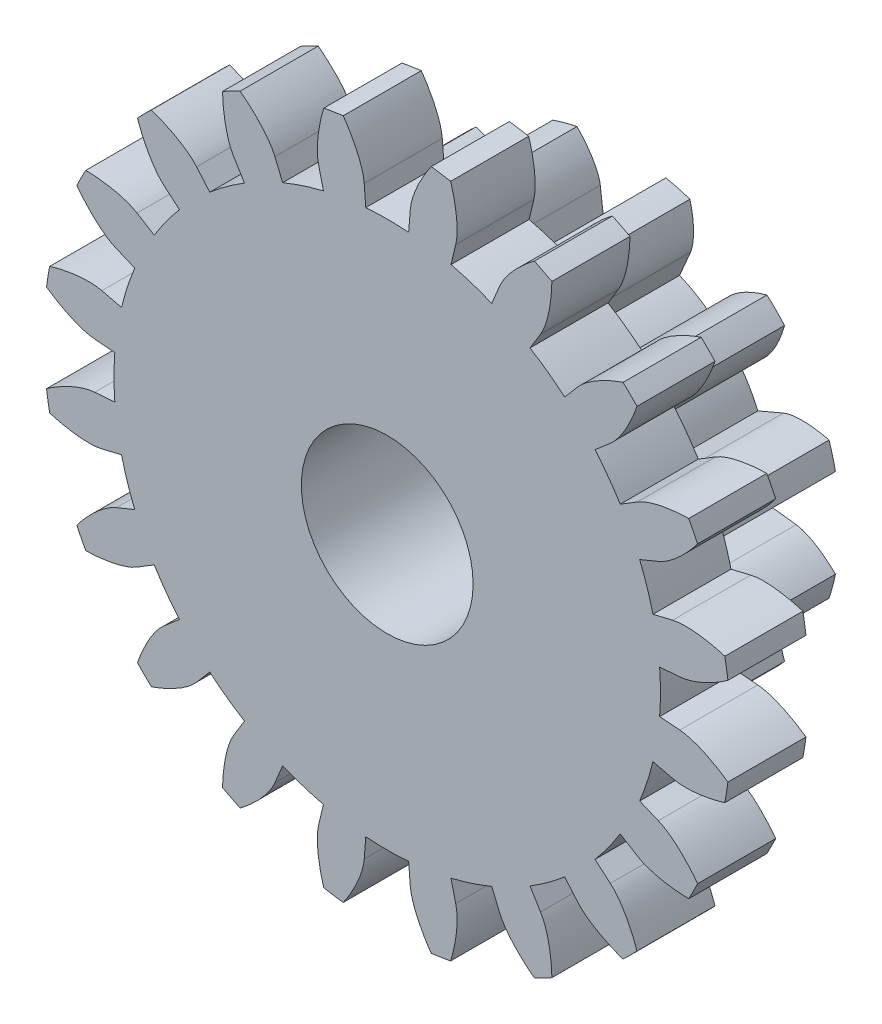
SolidWorks part; units mm, degrees
ref_plane "前视基准面" through (0, 0, 0) normal (0, 0, 1) x (1, 0, 0)
ref_plane "上视基准面" through (0, 0, 0) normal (0, 1, 0) x (1, 0, 0)
ref_plane "右视基准面" through (0, 0, 0) normal (1, 0, 0) x (0, 0, -1)
other "Configuration Table"
sketch "草图1" plane through (0, 0, 0) normal (0, 0, 1) x (1, 0, 0)
  line L0 (0, 0) -> (2.4, 0) construction
  line L1 (0, 0) -> (2.3795, 0.3133) construction
  line L2 (0, 0) -> (2.2389, 0.2708)
  line L3 (2.3795, 0.3133) -> (2.3795, -0.3133) construction
  line L4 (0, 0) -> (2.2389, -0.2708)
  circle A0 centre (0, 0) radius 2.8
  circle A1 centre (0, 0) radius 2.4 construction
  circle A2 centre (0, 0) radius 1.9
  circle A3 centre (0, 0) radius 2.2553 construction
  circle A4 centre (0, 0) radius 1.1
  spline S0 degree 4 poles (2.2389, 0.2708) (2.256, 0.2729) (2.3032, 0.2822) (2.3898, 0.3139) (2.5219, 0.3841) (2.677, 0.5007) (2.853, 0.6771) (3.026, 0.9126) (3.1769, 1.1958) (3.2958, 1.5205) (3.3736, 1.8571) (3.4129, 2.2003) (3.4163, 2.5627) (3.3737, 3.0095) (3.2548, 3.5322) (3.0297, 4.1132) (2.6825, 4.712) (2.2536, 5.2545) (1.7547, 5.7338) (1.2004, 6.1457) (0.5978, 6.4869) (-0.0359, 6.7564) (-0.7028, 6.9531) (-1.2893, 7.0628) (-1.8174, 7.1117) (-2.1968, 7.1243) (-2.5345, 7.1178) (-2.7579, 7.1054) (-3.0723, 7.0787) (-3.3085, 7.0447) (-3.5446, 7.0083) (-3.6626, 6.9826) (-3.7388, 6.968) knots 0 0 0 0 0 0.005604 0.015718 0.02996 0.048734 0.068727 0.096889 0.125051 0.153212 0.181374 0.209535 0.237696 0.271429 0.327752 0.384075 0.440398 0.496721 0.553044 0.609367 0.66569 0.722013 0.778336 0.834659 0.86282 0.890982 0.909091 0.931818 0.954545 0.977273 1 1 1 1 1 construction
  spline S1 degree 4 poles (2.2389, 0.2708) (2.256, 0.2729) (2.3032, 0.2822) (2.3898, 0.3139) (2.5219, 0.3841) (2.677, 0.5007) (2.853, 0.6771) (3.026, 0.9126) (3.1769, 1.1958) (3.2958, 1.5205) (3.3736, 1.8571) (3.4129, 2.2003) (3.4163, 2.5627) (3.3737, 3.0095) (3.2548, 3.5322) (3.0297, 4.1132) (2.6825, 4.712) (2.2536, 5.2545) (1.7547, 5.7338) (1.2004, 6.1457) (0.5978, 6.4869) (-0.0359, 6.7564) (-0.7028, 6.9531) (-1.2893, 7.0628) (-1.8174, 7.1117) (-2.1968, 7.1243) (-2.4555, 7.1193) (-2.5841, 7.1141) (-2.6344, 7.1115) knots 0 0 0 0 0 0.005604 0.015718 0.02996 0.048734 0.068727 0.096889 0.125051 0.153212 0.181374 0.209535 0.237696 0.271429 0.327752 0.384075 0.440398 0.496721 0.553044 0.609367 0.66569 0.722013 0.778336 0.834659 0.86282 0.890982 0.909091 0.909091 0.909091 0.909091 0.909091
  spline S2 degree 4 poles (2.2389, -0.2708) (2.256, -0.2729) (2.3032, -0.2822) (2.3898, -0.3139) (2.5219, -0.3841) (2.677, -0.5007) (2.853, -0.6771) (3.026, -0.9126) (3.1769, -1.1958) (3.2958, -1.5205) (3.3736, -1.8571) (3.4129, -2.2003) (3.4163, -2.5627) (3.3737, -3.0095) (3.2548, -3.5322) (3.0297, -4.1132) (2.6825, -4.712) (2.2536, -5.2545) (1.7547, -5.7338) (1.2004, -6.1457) (0.5978, -6.4869) (-0.0359, -6.7564) (-0.7028, -6.9531) (-1.2893, -7.0628) (-1.8174, -7.1117) (-2.1968, -7.1243) (-2.5345, -7.1178) (-2.7579, -7.1054) (-3.0723, -7.0787) (-3.3085, -7.0447) (-3.5446, -7.0083) (-3.6626, -6.9826) (-3.7388, -6.968) knots 0 0 0 0 0 0.005604 0.015718 0.02996 0.048734 0.068727 0.096889 0.125051 0.153212 0.181374 0.209535 0.237696 0.271429 0.327752 0.384075 0.440398 0.496721 0.553044 0.609367 0.66569 0.722013 0.778336 0.834659 0.86282 0.890982 0.909091 0.931818 0.954545 0.977273 1 1 1 1 1 construction
  spline S3 degree 4 poles (2.2389, -0.2708) (2.256, -0.2729) (2.3032, -0.2822) (2.3898, -0.3139) (2.5219, -0.3841) (2.677, -0.5007) (2.853, -0.6771) (3.026, -0.9126) (3.1769, -1.1958) (3.2958, -1.5205) (3.3736, -1.8571) (3.4129, -2.2003) (3.4163, -2.5627) (3.3737, -3.0095) (3.2548, -3.5322) (3.0297, -4.1132) (2.6825, -4.712) (2.2536, -5.2545) (1.7547, -5.7338) (1.2004, -6.1457) (0.5978, -6.4869) (-0.0359, -6.7564) (-0.7028, -6.9531) (-1.2893, -7.0628) (-1.8174, -7.1117) (-2.1968, -7.1243) (-2.4555, -7.1193) (-2.5841, -7.1141) (-2.6344, -7.1115) knots 0 0 0 0 0 0.005604 0.015718 0.02996 0.048734 0.068727 0.096889 0.125051 0.153212 0.181374 0.209535 0.237696 0.271429 0.327752 0.384075 0.440398 0.496721 0.553044 0.609367 0.66569 0.722013 0.778336 0.834659 0.86282 0.890982 0.909091 0.909091 0.909091 0.909091 0.909091
  point P15 (2.3795, 0)
  dimension "齿顶圆直径" = 5.6
  dimension "分度圆直径" = 4.8
  dimension "齿根圆直径" = 3.8
  dimension "基圆直径" = 4.5105
  dimension "内孔直径" = 2.2
  dimension "渐近线镜像线夹角" = 7.5
extrude "凸台-拉伸1" add sketch "草图1" along normal blind 2 contours A0 | A4
extrude "切除-拉伸1" cut sketch "草图1<3>" along normal through all contours A2 S3 A0 S1 region at (2.4126, 0, 0)
sketch "草图1<3>" plane through (0, 0, 0) normal (0, 0, 1) x (1, 0, 0) same geometry as "草图1"
pattern_circular "阵列(圆周)1" count 12 every 30 about axis through (0, 0, 2) along (0, 0, 1) of "切除-拉伸1"
sketch "草图2" plane through (0, 0, 2) normal (0, 0, 1) x (1, 0, 0)
  line L0 (0, 0) -> (4, 0) construction
  line L1 (0, 0) -> (3.7472, 0.2949)
  line L2 (0, 0) -> (3.7472, -0.2949)
  line L3 (3.7472, 0.2949) -> (3.7472, -0.2949) construction
  circle A0 centre (0, 0) radius 4 construction
  circle A1 centre (0, 0) radius 3.7588 construction
  circle A2 centre (0, 0) radius 3.5
  circle A3 centre (0, 0) radius 4.4
  circle A4 centre (0, 0) radius 1.1
  spline S0 degree 4 poles (3.7472, -0.2949) (3.7757, -0.2972) (3.855, -0.3094) (4.0015, -0.3561) (4.2262, -0.4638) (4.4927, -0.6472) (4.798, -0.9286) (5.1025, -1.3087) (5.3735, -1.7697) (5.6493, -2.4352) (5.8125, -3.1386) (5.8752, -3.8856) (5.8277, -4.7763) (5.6663, -5.6549) (5.3317, -6.638) (4.7957, -7.6594) (4.1188, -8.5926) (3.3223, -9.4257) (2.4264, -10.1501) (1.4493, -10.7604) (0.4087, -11.2532) (-0.5446, -11.5806) (-1.3119, -11.7698) (-1.8783, -11.8732) (-2.2315, -11.9257) (-2.5216, -11.9603) (-2.7979, -11.9879) (-3.1018, -12.008) (-3.336, -12.0203) (-3.6054, -12.0257) (-3.8772, -12.0273) (-4.1494, -12.0219) (-4.6264, -12.0016) (-5.0143, -11.9616) (-5.4165, -11.9173) (-5.6106, -11.8828) (-5.7404, -11.8638) knots 0 0 0 0 0 0.005604 0.015718 0.02996 0.048734 0.068727 0.096889 0.125051 0.153212 0.209535 0.237696 0.271429 0.327752 0.384075 0.440398 0.496721 0.553044 0.609367 0.66569 0.722013 0.778336 0.806497 0.820578 0.834659 0.84874 0.86282 0.876901 0.890982 0.900036 0.909091 0.931818 0.954545 0.977273 1 1 1 1 1 construction
  spline S1 degree 4 poles (3.7472, -0.2949) (3.7757, -0.2972) (3.855, -0.3094) (4.0015, -0.3561) (4.2262, -0.4638) (4.4927, -0.6472) (4.798, -0.9286) (5.1025, -1.3087) (5.3735, -1.7697) (5.6493, -2.4352) (5.8125, -3.1386) (5.8752, -3.8856) (5.8277, -4.7763) (5.6663, -5.6549) (5.3317, -6.638) (4.7957, -7.6594) (4.1188, -8.5926) (3.3223, -9.4257) (2.4264, -10.1501) (1.4493, -10.7604) (0.4087, -11.2532) (-0.5446, -11.5806) (-1.3119, -11.7698) (-1.8783, -11.8732) (-2.2315, -11.9257) (-2.5216, -11.9603) (-2.7979, -11.9879) (-3.1018, -12.008) (-3.336, -12.0203) (-3.6054, -12.0257) (-3.7647, -12.0266) (-3.849, -12.0262) (-3.891, -12.0258) knots 0 0 0 0 0 0.005604 0.015718 0.02996 0.048734 0.068727 0.096889 0.125051 0.153212 0.209535 0.237696 0.271429 0.327752 0.384075 0.440398 0.496721 0.553044 0.609367 0.66569 0.722013 0.778336 0.806497 0.820578 0.834659 0.84874 0.86282 0.876901 0.890982 0.900036 0.909091 0.909091 0.909091 0.909091 0.909091
  spline S2 degree 4 poles (3.7472, 0.2949) (3.7757, 0.2972) (3.855, 0.3094) (4.0015, 0.3561) (4.2262, 0.4638) (4.4927, 0.6472) (4.798, 0.9286) (5.1025, 1.3087) (5.3735, 1.7697) (5.6493, 2.4352) (5.8125, 3.1386) (5.8752, 3.8856) (5.8277, 4.7763) (5.6663, 5.6549) (5.3317, 6.638) (4.7957, 7.6594) (4.1188, 8.5926) (3.3223, 9.4257) (2.4264, 10.1501) (1.4493, 10.7604) (0.4087, 11.2532) (-0.5446, 11.5806) (-1.3119, 11.7698) (-1.8783, 11.8732) (-2.2315, 11.9257) (-2.5216, 11.9603) (-2.7979, 11.9879) (-3.1018, 12.008) (-3.336, 12.0203) (-3.6054, 12.0257) (-3.8772, 12.0273) (-4.1494, 12.0219) (-4.6264, 12.0016) (-5.0143, 11.9616) (-5.4165, 11.9173) (-5.6106, 11.8828) (-5.7404, 11.8638) knots 0 0 0 0 0 0.005604 0.015718 0.02996 0.048734 0.068727 0.096889 0.125051 0.153212 0.209535 0.237696 0.271429 0.327752 0.384075 0.440398 0.496721 0.553044 0.609367 0.66569 0.722013 0.778336 0.806497 0.820578 0.834659 0.84874 0.86282 0.876901 0.890982 0.900036 0.909091 0.931818 0.954545 0.977273 1 1 1 1 1 construction
  spline S3 degree 4 poles (3.7472, 0.2949) (3.7757, 0.2972) (3.855, 0.3094) (4.0015, 0.3561) (4.2262, 0.4638) (4.4927, 0.6472) (4.798, 0.9286) (5.1025, 1.3087) (5.3735, 1.7697) (5.6493, 2.4352) (5.8125, 3.1386) (5.8752, 3.8856) (5.8277, 4.7763) (5.6663, 5.6549) (5.3317, 6.638) (4.7957, 7.6594) (4.1188, 8.5926) (3.3223, 9.4257) (2.4264, 10.1501) (1.4493, 10.7604) (0.4087, 11.2532) (-0.5446, 11.5806) (-1.3119, 11.7698) (-1.8783, 11.8732) (-2.2315, 11.9257) (-2.5216, 11.9603) (-2.7979, 11.9879) (-3.1018, 12.008) (-3.336, 12.0203) (-3.6054, 12.0257) (-3.7647, 12.0266) (-3.849, 12.0262) (-3.891, 12.0258) knots 0 0 0 0 0 0.005604 0.015718 0.02996 0.048734 0.068727 0.096889 0.125051 0.153212 0.209535 0.237696 0.271429 0.327752 0.384075 0.440398 0.496721 0.553044 0.609367 0.66569 0.722013 0.778336 0.806497 0.820578 0.834659 0.84874 0.86282 0.876901 0.890982 0.900036 0.909091 0.909091 0.909091 0.909091 0.909091
  point P16 (3.7472, 0)
  dimension "内孔直径" = 2.2
  dimension "分度圆直径" = 8
  dimension "齿顶圆直径" = 8.8
  dimension "基圆直径" = 7.5175
  dimension "齿根圆直径" = 7
  dimension "渐开线镜像线夹角" = 4.5
extrude "凸台-拉伸2" add sketch "草图2" along normal blind 1 contours A3 | A4
extrude "切除-拉伸3" cut sketch "草图2<3>" along normal through all contours S3 L1 A2 L2 S1 A3 region at (4.0017, 0, 2)
sketch "草图2<3>" plane through (0, 0, 2) normal (0, 0, 1) x (1, 0, 0) same geometry as "草图2"
pattern_circular "阵列(圆周)2" count 20 over 360 about axis through (0, 0, 3) along (0, 0, 1) of "切除-拉伸3"
equation "\"m\"= 0.4'模数"
equation "\"z\" = 12'齿数"
equation "\"a\"= 20度'压力角"
equation "\"d\"= \"m\" * \"z\"'分度圆直径"
equation "\"da\"= ( \"z\" + 2 ) * \"m\"'齿顶圆直径"
equation "\"df\"= ( \"z\" - 2.5 ) * \"m\"'齿根圆直径"
equation "\"s\"= 0.5 * PI * \"m\"'分度圆齿厚"
equation "\"r\"= 0.38 * \"m\"'齿根圆角"
equation "\"B\"= 0.3 * \"d\"'齿厚"
equation "\"db\"= \"m\" * \"z\" * cos ( \"a\" )'基圆直径"
equation "\"rb\"= \"db\" / 2'基圆半径"
equation "\"齿顶圆直径@草图1\"= \"da\""
equation "\"分度圆直径@草图1\"= \"d\""
equation "\"齿根圆直径@草图1\"= \"df\""
equation "\"基圆直径@草图1\"= \"db\""
equation "\"渐近线镜像线夹角@草图1\"= 360 / 4 / \"z\""
equation "\"h\" = 2'齿轮厚度"
equation "\"ir\"= 2.2mm'内孔直径"
equation "\"内孔直径@草图1\"= \"ir\""
equation "\"齿轮厚@凸台-拉伸1\"= \"h\""
equation "\"齿轮夹角@阵列(圆周)1\"= 360 / \"z\""
equation "\"齿数@阵列(圆周)1\"= \"z\""
equation "\"m1\"= 0.4'模数"
equation "\"z1\" = 20'齿数"
equation "\"a1\"= 20度'压力角"
equation "\"d1\"= \"m1\" * \"z1\"'分度圆直径"
equation "\"da1\"= ( \"z1\" + 2 ) * \"m1\"'齿顶圆直径"
equation "\"df1\"= ( \"z1\" - 2.5 ) * \"m1\"'齿根圆直径"
equation "\"s1\"= 0.5 * PI * \"m1\"'分度圆齿厚"
equation "\"r1\"= 0.38 * \"m1\"'齿根圆角"
equation "\"B1\"= 0.3 * \"d1\"'齿厚"
equation "\"db1\"= \"m1\" * \"z1\" * cos ( \"a1\" )'基圆直径"
equation "\"rb1\"= \"db1\" / 2'基圆半径"
equation "\"分度圆直径@草图2\"= \"d1\""
equation "\"齿顶圆直径@草图2\"= \"da1\""
equation "\"基圆直径@草图2\"= \"db1\""
equation "\"齿根圆直径@草图2\"= \"df1\""
equation "\"渐开线镜像线夹角@草图2\"= 360 / 4 / \"z1\""
equation "\"内孔直径@草图2\"= \"ir\""
equation "\"二层齿轮厚@凸台-拉伸2\" = \"h1\""
equation "\"h1\"= 1'齿轮厚度"
equation "\"二层齿数@阵列(圆周)2\"= \"z1\""
